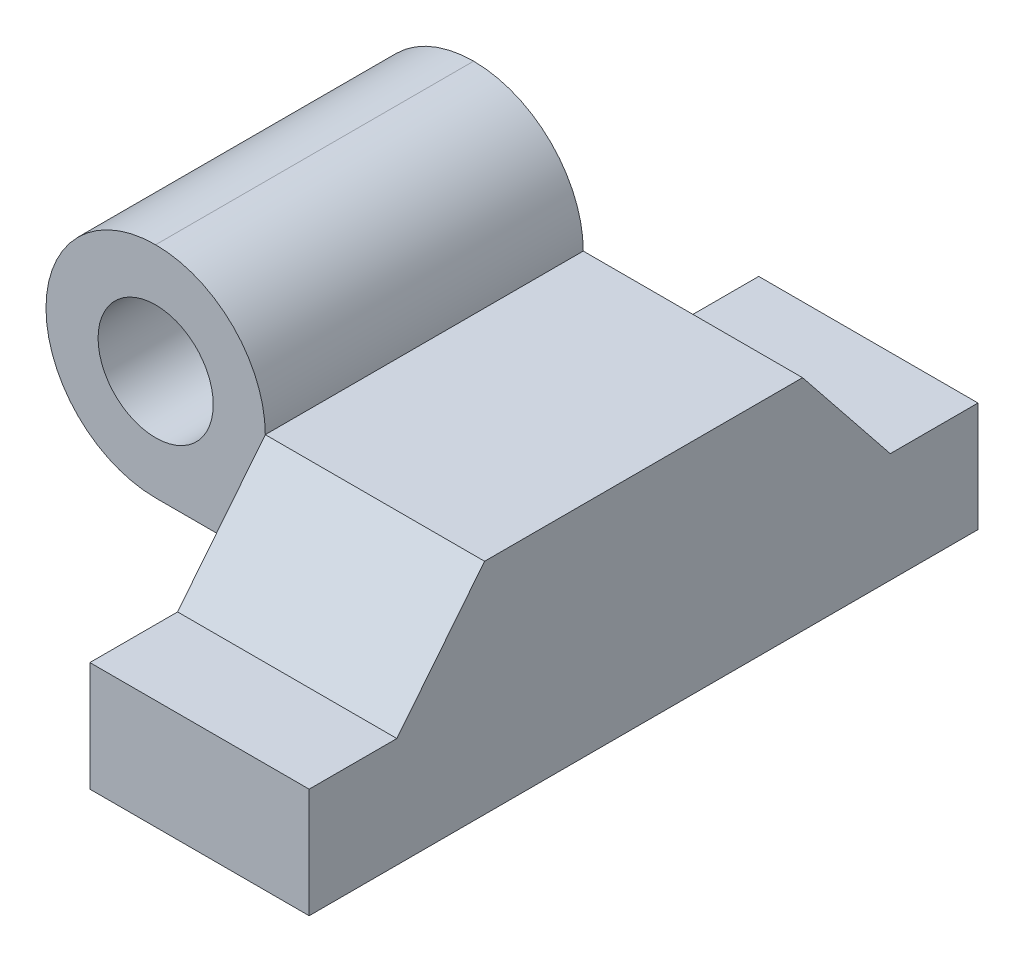
SolidWorks part; units mm, degrees
ref_plane "Front Plane" through (0, 0, 0) normal (0, 0, 1) x (1, 0, 0)
ref_plane "Top Plane" through (0, 0, 0) normal (0, 1, 0) x (1, 0, 0)
ref_plane "Right Plane" through (0, 0, 0) normal (1, 0, 0) x (0, 0, -1)
sketch "Sketch1" plane through (0, 0, 0) normal (0, 1, 0) x (1, 0, 0)
  line L1 (-6, -9.15) -> (6, -9.15)
  line L2 (-6, -9.15) -> (-6, 9.15)
  line L3 (-6, 9.15) -> (6, 9.15)
  line L4 (6, -9.15) -> (6, 9.15)
  line L5 (-6, -9.15) -> (6, 9.15) construction
  line L6 (-6, 9.15) -> (6, -9.15) construction
  point P0 (0, 0)
  dimension "D1" = 12
  dimension "D2" = 18.3
extrude "Boss-Extrude1" add sketch "Sketch1" along normal blind 3
sketch "Sketch2" plane through (0, 3, 0) normal (0, 1, 0) x (1, 0, 0)
  line L1 (-6, 4.35) -> (0, 4.35)
  line L2 (-6, 4.35) -> (-6, -4.35)
  line L3 (-6, -4.35) -> (0, -4.35)
  line L4 (0, 4.35) -> (0, -4.35)
  line L5 (6, -9.15) -> (6, 9.15) construction
  point P10 (6, 0)
  point P11 (0, 0)
  dimension "D1" = 6
  dimension "D2" = 8.7
extrude "Boss-Extrude2" add sketch "Sketch2" along normal blind 6
sketch "Sketch3" plane through (0, 0, 9.15) normal (0, 0, 1) x (1, 0, 0)
  line L0 (-6, 9) -> (0, 9) construction
  line L1 (-6, 0) -> (6, 0) construction
  circle A0 centre (-3, 6) radius 1.575
  point P5 (-3, 9)
  dimension "D1" = 3.15
  dimension "D2" = 6
extrude "Cut-Extrude1" cut sketch "Sketch3" against normal through all
fillet "Fillet1" radius 3 2 edges at (-6, 9, 0) (0, 9, 0)
sketch "Sketch4" plane through (0, 3, 0) normal (0, 1, 0) x (1, 0, 0)
  line L0 (6, -9.15) -> (6, 9.15) construction
  line L1 (0, -4.35) -> (6, -4.35)
  line L2 (0, -4.35) -> (0, 4.35)
  line L3 (0, 4.35) -> (6, 4.35)
  line L4 (6, -4.35) -> (6, 4.35)
  line L5 (-1.425, 4.35) -> (-4.575, 4.35) construction
extrude "Boss-Extrude3" add sketch "Sketch4" along normal blind 3
sketch "Sketch5" plane through (0, 0, 0) normal (0, -1, 0) x (1, 0, 0)
  line L0 (6, -9.15) -> (-6, -9.15) construction
  line L1 (-6, 9.15) -> (0, 9.15)
  line L2 (-6, 9.15) -> (-6, -9.15)
  line L3 (-6, -9.15) -> (0, -9.15)
  line L4 (0, 9.15) -> (0, -9.15)
  line L5 (0, -4.35) -> (0, 4.35) construction
extrude "Cut-Extrude2" cut sketch "Sketch5" against normal blind 3
fillet "Fillet2" radius 3 1 edges at (-6, 3, 0)
sketch "Sketch6" plane through (6, 0, 0) normal (1, 0, 0) x (0, 0, -1)
  line L0 (4.35, 3) -> (6.75, 3)
  line L1 (4.35, 3) -> (9.15, 3) construction
  line L2 (6.75, 3) -> (4.35, 6)
  line L3 (4.35, 6) -> (4.35, 3)
  line L4 (-4.35, 3) -> (-4.35, 6)
  line L5 (-4.35, 6) -> (-6.75, 3)
  line L6 (-9.15, 3) -> (-4.35, 3) construction
  line L7 (-6.75, 3) -> (-4.35, 3)
  point P11 (-6.75, 3)
  point P15 (-6.75, 3)
extrude "Boss-Extrude4" add sketch "Sketch6" against normal up to surface (6 mm away) up to face at (0, 2, 0)
